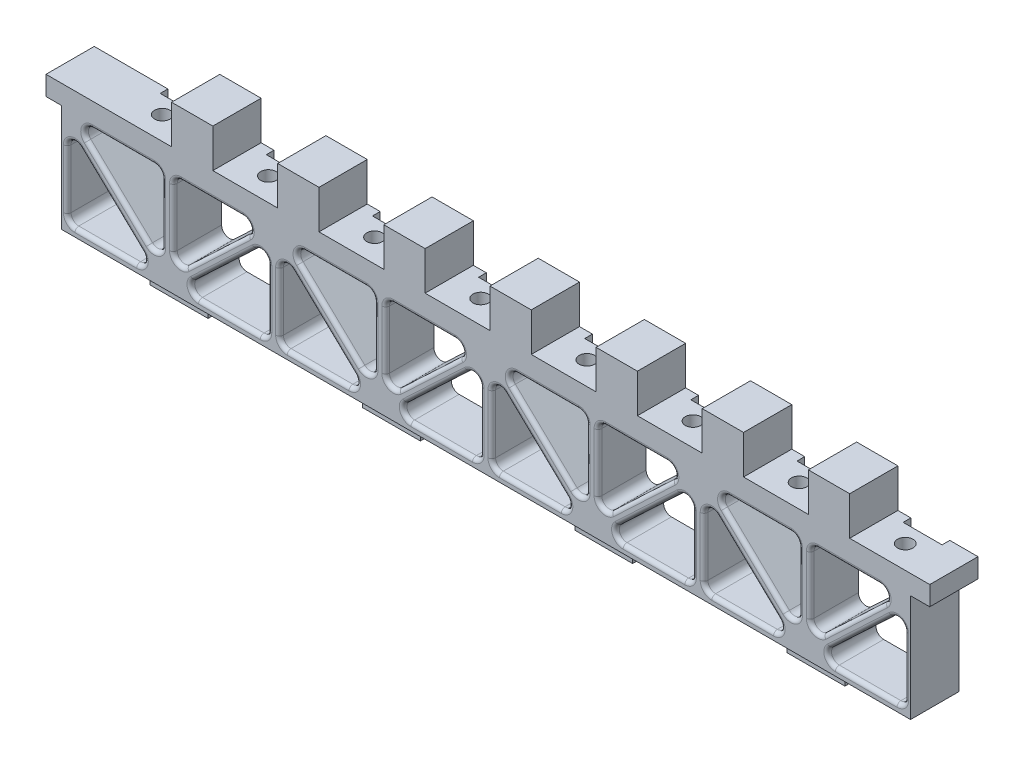
SolidWorks part; units mm, degrees
ref_plane "Front Plane" through (0, 0, 0) normal (0, 0, 1) x (1, 0, 0)
ref_plane "Top Plane" through (0, 0, 0) normal (0, 1, 0) x (1, 0, 0)
ref_plane "Right Plane" through (0, 0, 0) normal (1, 0, 0) x (0, 0, -1)
sketch "Sketch1" plane through (0, 0, 0) normal (0, 1, 0) x (1, 0, 0)
  line L1 (0, 0) -> (228.98, 0)
  line L2 (0, 0) -> (0, 12.5)
  line L3 (0, 12.5) -> (228.98, 12.5)
  line L4 (228.98, 0) -> (228.98, 12.5)
  dimension "D1" = 12.5
  dimension "D2" = 228.98
extrude "Boss-Extrude1" add sketch "Sketch1" along normal blind 5
sketch "Sketch2" plane through (0, 5, 0) normal (0, 1, 0) x (1, 0, 0)
  line L0 (228.98, 12.5) -> (0, 12.5) construction
  line L1 (19.08, 12.5) -> (29.18, 12.5)
  line L2 (19.08, 12.5) -> (19.08, 10.5)
  line L3 (19.08, 10.5) -> (29.18, 10.5)
  line L4 (29.18, 12.5) -> (29.18, 10.5)
  line L5 (0, 12.5) -> (0, 0) construction
  dimension "D1" = 19.08
  dimension "D2" = 10.1
  dimension "D3" = 2
sketch "Sketch3" plane through (0, 5, 0) normal (0, 1, 0) x (1, 0, 0)
  line L0 (0, 0) -> (228.98, 0) construction
  line L1 (19.08, 12.5) -> (19.08, 10.5) construction
  circle A0 centre (24.13, 6) radius 2
  dimension "D1" = 4
  dimension "D2" = 6
  dimension "D3" = 5.05
extrude "Cut-Extrude1" cut sketch "Sketch2" against normal blind 3.05
extrude "Cut-Extrude2" cut sketch "Sketch3" against normal blind 4
pattern_linear "LPattern1" count 8 spacing 27.5 along (1, 0, 0) of "Cut-Extrude1", "Cut-Extrude2"
sketch "Sketch4" plane through (0, 0, 0) normal (0, 0, 1) x (1, 0, 0)
  line L1 (4, 0.2046) -> (31.5, 0.2046)
  line L2 (4, 0.2046) -> (4, -27.7954)
  line L3 (4, -27.7954) -> (31.5, -27.7954)
  line L4 (31.5, 0.2046) -> (31.5, 0)
  line L5 (30, -1.2954) -> (7, -1.2954)
  line L6 (7, -1.2954) -> (30, -23.1973)
  line L7 (30, -23.1973) -> (30, -1.2954)
  line L8 (5.5, -3.8935) -> (5.5, -25.7954)
  line L9 (5.5, -25.7954) -> (28.5, -25.7954)
  line L10 (28.5, -25.7954) -> (5.5, -3.8935)
  line L11 (0, 5) -> (0, 0) construction
  line L12 (0, 0) -> (228.98, 0) construction
  line L13 (31.5, -27.7954) -> (59, -27.7954)
  line L15 (31.5, 0) -> (59, 0)
  line L16 (59, -27.7954) -> (59, 0)
  line L17 (33, -1.5) -> (33, -23.1973)
  line L18 (33, -23.1973) -> (56, -1.5)
  line L19 (56, -1.5) -> (33, -1.5)
  line L20 (34.5, -25.7954) -> (57.5, -25.7954)
  line L21 (57.5, -25.7954) -> (57.5, -4.0981)
  line L22 (57.5, -4.0981) -> (34.5, -25.7954)
  dimension "D1" = 28
  dimension "D2" = 27.5
  dimension "D3" = 1.5
  dimension "D4" = 1.5
  dimension "D5" = 2
  dimension "D6" = 1.5
  dimension "D7" = 3
  dimension "D8" = 3
  dimension "D9" = 4
  dimension "D10" = 27.5
  dimension "D11" = 1.5
  dimension "D12" = 1.5
  dimension "D13" = 1.5
  dimension "D14" = 3
  dimension "D15" = 3
  dimension "D16" = 1.5
  dimension "D17" = 1.5
  dimension "D18" = 1.5
  dimension "D19" = 1.5
extrude "Boss-Extrude2" add sketch "Sketch4" against normal blind 12.5
fillet "Fillet1" radius 2 12 edges at (57.5, -25.7954, -6.25) (57.5, -4.0981, -6.25) (30, -1.2954, -6.25) (33, -1.5, -6.25) (56, -1.5, -6.25) (5.5, -25.7954, -6.25) (5.5, -3.8935, -6.25) (7, -1.2954, -6.25) (34.5, -25.7954, -6.25) (28.5, -25.7954, -6.25) (30, -23.1973, -6.25) (33, -23.1973, -6.25)
fillet "Fillet2" radius 1 24 edges at (25.3565, -24.5381, 0) (15.4998, -25.7954, 0) (6.0858, -25.2096, 0) (5.5, -16.1776, 0) (6.7121, -6.7215, 0) (56.2922, -6.8979, 0) (57.5, -16.2649, 0) (56.9142, -25.2096, 0) (47.5173, -25.7954, 0) (37.6759, -24.5338, 0) (34.2078, -20.3975, 0) (33, -11.0306, 0) (33.5858, -2.0858, 0) (42.9827, -1.5, 0) (52.8241, -2.7616, 0) (28.7879, -20.3693, 0) (18.621, -12.3616, 0) (10.1435, -2.5527, 0) (20.0002, -1.2954, 0) (29.4142, -1.8812, 0) (16.879, -14.7292, 0) (46.1449, -14.81, 0) (44.3551, -12.4854, 0) (30, -10.9132, 0)
sketch "Sketch5" plane through (0, -27.7954, 0) normal (0, -1, 0) x (1, 0, 0)
  line L0 (4, 0) -> (59, 0) construction
  line L1 (24, -3) -> (39, -3)
  line L2 (24, -3) -> (24, -9.4)
  line L3 (24, -9.4) -> (39, -9.4)
  line L4 (39, -3) -> (39, -9.4)
  line L8 (4, 0) -> (4, -12.5) construction
  dimension "D1" = 6.4
  dimension "D2" = 3
  dimension "D3" = 15
  dimension "D4" = 20
extrude "Boss-Extrude3" add sketch "Sketch5" along normal blind 4
pattern_linear "LPattern2" count 4 spacing 55 along (1, 0, 0) of "Boss-Extrude2", "Fillet1", "Fillet2", "Boss-Extrude3"
sketch "Sketch6" plane through (0, 5, 0) normal (0, 1, 0) x (1, 0, 0)
  line L0 (46.58, 12.5) -> (29.18, 12.5) construction
  line L1 (32.53, 12.5) -> (43.23, 12.5)
  line L2 (32.53, 12.5) -> (32.53, 0)
  line L3 (32.53, 0) -> (43.23, 0)
  line L4 (43.23, 12.5) -> (43.23, 0)
  line L5 (0, 0) -> (228.98, 0) construction
  line L6 (29.18, 10.5) -> (29.18, 12.5) construction
  line L7 (46.58, 12.5) -> (46.58, 10.5) construction
  dimension "D1" = 3.35
  dimension "D2" = 3.35
extrude "Boss-Extrude4" add sketch "Sketch6" along normal blind 10
pattern_linear "LPattern3" count 7 spacing 27.5 along (1, 0, 0) of "Boss-Extrude4"
